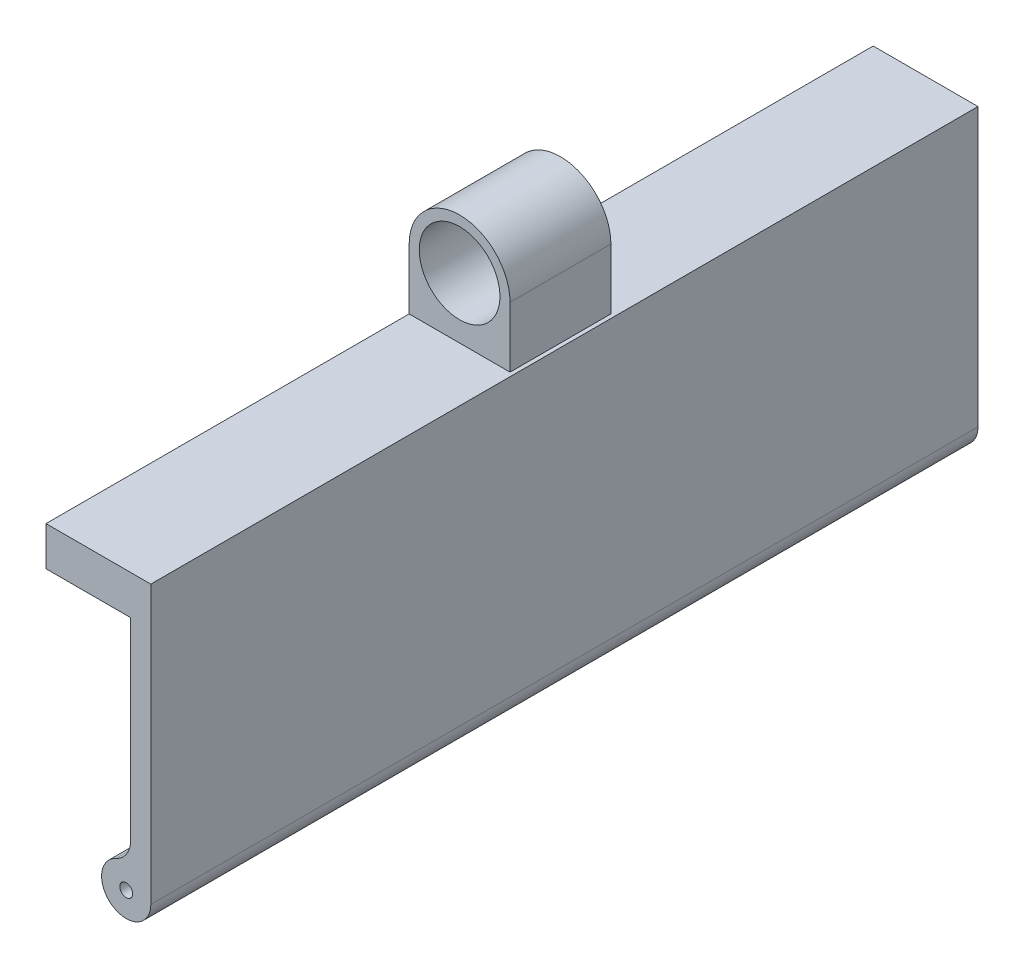
SolidWorks part; units mm, degrees
ref_plane "Front Plane" through (0, 0, 0) normal (0, 0, 1) x (1, 0, 0)
ref_plane "Top Plane" through (0, 0, 0) normal (0, 1, 0) x (1, 0, 0)
ref_plane "Right Plane" through (0, 0, 0) normal (1, 0, 0) x (0, 0, -1)
sketch "Sketch1" plane through (0, 0, 0) normal (0, 0, 1) x (1, 0, 0)
  line L0 (0, 0) -> (3.1723, 0) construction
  line L1 (2.44, 0) -> (2.44, 25)
  line L2 (0.44, 4.49) -> (0.44, 25)
  line L3 (0.44, 25) -> (2.44, 25)
  circle A0 centre (0, 0) radius 0.64
  arc A1 (-1.0175, 2.2177) -> (2.44, 0) centre (0, 0) ccw
  arc A2 (0.44, 4.49) -> (-1.0175, 2.2177) centre (-2.06, 4.49) cw
  dimension "D1" = 1.28
  dimension "D2" = 4.88
  dimension "D5" = 2.5
  dimension "D3" = 25
  dimension "D4" = 2
extrude "Boss-Extrude1" add sketch "Sketch1" along normal blind 82
sketch "Sketch3" plane through (0, 25, 0) normal (0, 1, 0) x (1, 0, 0)
  line L1 (0.44, -82) -> (2.44, -82)
  line L2 (0.44, -82) -> (0.44, 0)
  line L3 (0.44, 0) -> (2.44, 0)
  line L4 (2.44, -82) -> (2.44, 0)
extrude "Boss-Extrude4" add sketch "Sketch3" along normal blind 2.5
sketch "Sketch6" plane through (0.44, 0, 0) normal (-1, 0, 0) x (0, 0, 1)
  line L1 (82, 27.5) -> (0, 27.5)
  line L2 (82, 27.5) -> (82, 23.6193)
  line L3 (82, 23.6193) -> (0, 23.6193)
  line L4 (0, 27.5) -> (0, 23.6193)
  dimension "D1" = 23.01
extrude "Boss-Extrude5" add sketch "Sketch6" along normal blind 8.39
ref_plane "Plane2" through (-7.95, 23.6193, 0) normal (0, 0, 1) x (1, 0, 0)
ref_plane "Plane3" through (-7.95, 23.6193, 82) normal (0, 0, 1) x (1, 0, 0)
ref_plane "Plane4" through (0.44, 23.6193, 82) normal (0, 0, 1) x (1, 0, 0)
sketch "Sketch8" plane through (0, 0, 0) normal (0, 0, -1) x (-1, 0, 0)
  line L0 (7.95, 27.5) -> (7.95, 33.5)
  line L1 (-2.05, 33.5) -> (-2.05, 27.5)
  line L2 (-2.44, 27.5) -> (7.95, 27.5) construction
  line L3 (7.95, 27.5) -> (-2.05, 27.5)
  circle A0 centre (2.95, 33.5) radius 4
  arc A1 (7.95, 33.5) -> (-2.05, 33.5) centre (2.95, 33.5) ccw
extrude "Boss-Extrude6" add sketch "Sketch8" against normal blind 10 from offset 36 offset against normal yes
